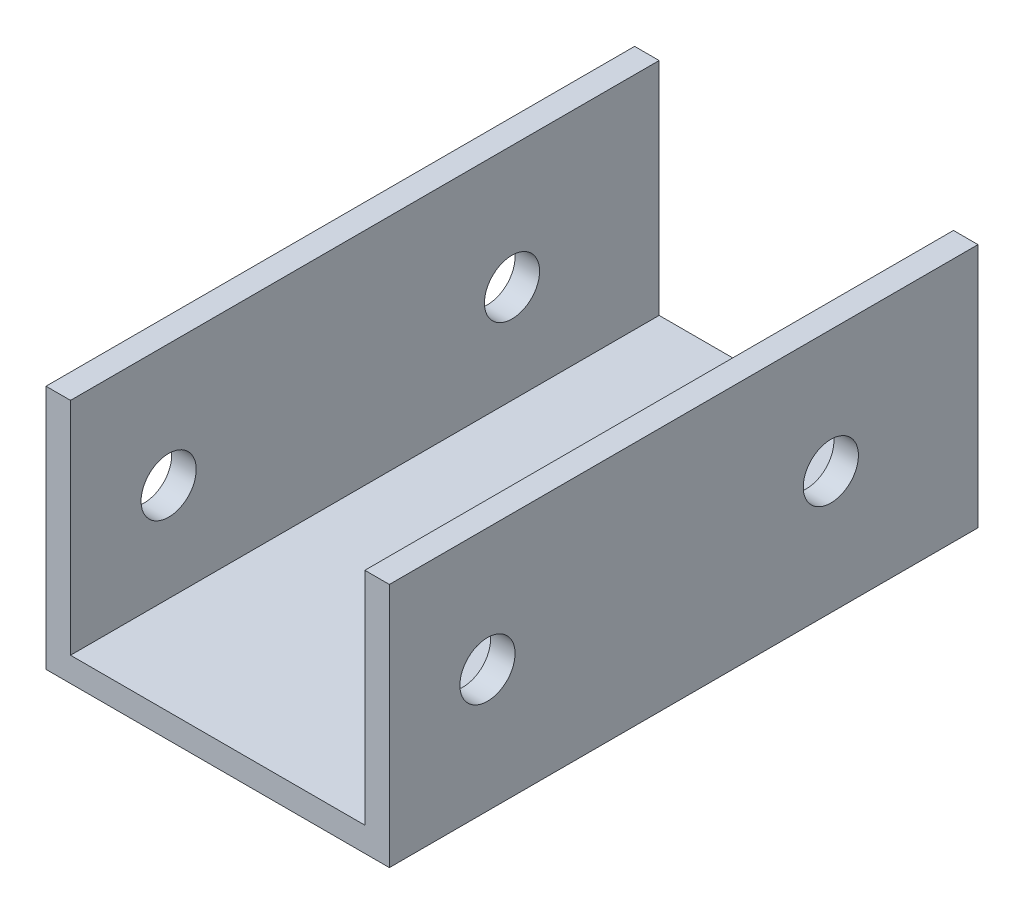
SolidWorks part; units mm, degrees
ref_plane "Front Plane" through (0, 0, 0) normal (0, 0, 1) x (1, 0, 0)
ref_plane "Top Plane" through (0, 0, 0) normal (0, 1, 0) x (1, 0, 0)
ref_plane "Right Plane" through (0, 0, 0) normal (1, 0, 0) x (0, 0, -1)
sketch "Sketch2" plane through (0, 0, 0) normal (0, 0, 1) x (1, 0, 0)
  line L1 (-22.225, 15.875) -> (22.225, 15.875)
  line L2 (-22.225, 15.875) -> (-22.225, -15.875)
  line L3 (-22.225, -15.875) -> (22.225, -15.875)
  line L4 (22.225, 15.875) -> (22.225, -15.875)
  line L5 (-22.225, 15.875) -> (22.225, -15.875) construction
  line L6 (-22.225, -15.875) -> (22.225, 15.875) construction
  line L7 (-19.05, 15.875) -> (19.05, 15.875)
  line L8 (-19.05, 15.875) -> (-19.05, -12.7)
  line L9 (-19.05, -12.7) -> (19.05, -12.7)
  line L10 (19.05, 15.875) -> (19.05, -12.7)
  point P0 (0, 0)
  point P10 (0, -12.7)
  dimension "D1" = 44.45
  dimension "D2" = 31.75
  dimension "D3" = 3.175
  dimension "D4" = 3.175
extrude "Boss-Extrude1" add sketch "Sketch2" along normal blind 76.2 contours L1 L10 L9 L8 L2 L3 L4 region at (-20.6375, 15.3288, 0)
hole_wizard "1/4 Clearance Hole1" positions "Sketch3" profile "Sketch4" hole size "1/4" standard "ANSI Inch" end condition through all
sketch "Sketch3" plane through (22.225, 0, 0) normal (1, 0, 0) x (0, 0, -1)
  line L0 (-76.2, -15.875) -> (-76.2, 0) construction
  line L1 (-76.2, 15.875) -> (-76.2, -15.875) construction
  line L2 (-76.2, 0) -> (-63.5, 0) construction
  line L3 (0, 15.875) -> (0, -15.875) construction
  point P7 (-63.5, 0)
  point P12 (-19.05, 0)
  dimension "D1" = 15.875
  dimension "D2" = 12.7
  dimension "D3" = 19.05
sketch "Sketch4" plane through (22.225, 0, 19.05) normal (0, 1, 0) x (0, 0, -1)
  line L0 (0, 0) -> (0, 44.45)
  line L1 (0, 44.45) -> (3.5712, 44.45)
  line L2 (3.5712, 44.45) -> (3.5712, 0)
  line L5 (3.5712, 0) -> (0, 0)
  line L11 (0, -6.35) -> (0, 107.95) construction
  dimension "Thru Hole Dia." = 7.1425
  dimension "Thru Hole Depth" = 44.45
